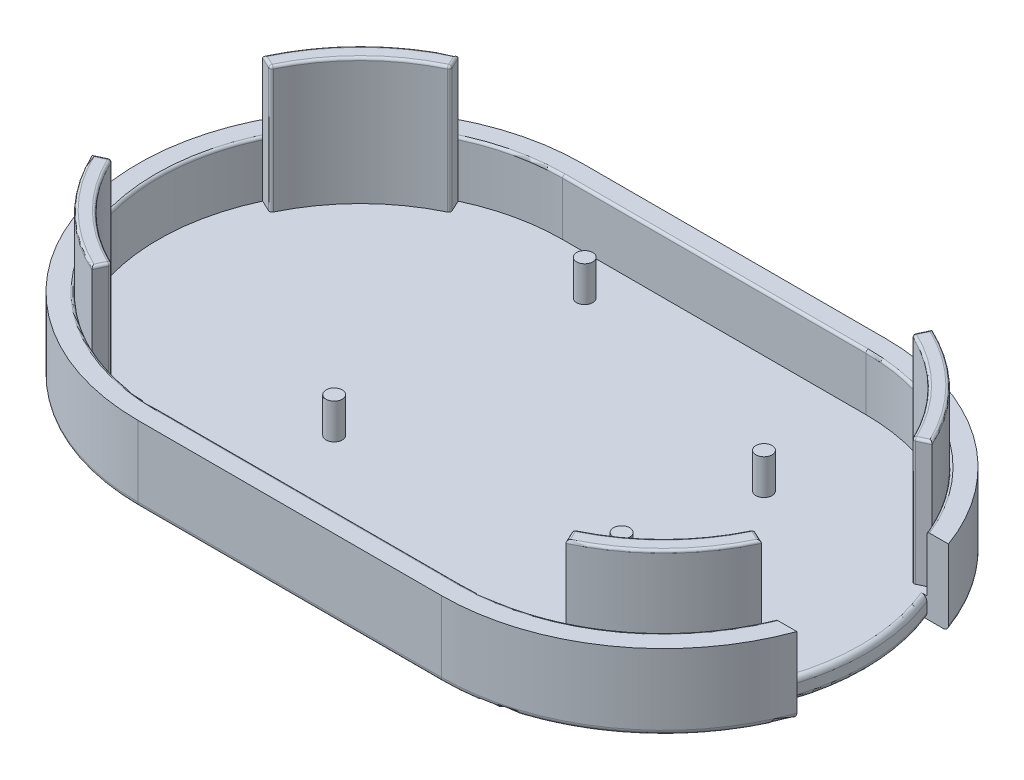
SolidWorks part; units mm, degrees
ref_plane "Front Plane" through (0, 0, 0) normal (0, 0, 1) x (1, 0, 0)
ref_plane "Top Plane" through (0, 0, 0) normal (0, 1, 0) x (1, 0, 0)
ref_plane "Right Plane" through (0, 0, 0) normal (1, 0, 0) x (0, 0, -1)
sketch "Sketch1" plane through (0, 0, 0) normal (0, 1, 0) x (1, 0, 0)
  line L1 (-30, 44) -> (30, 44)
  line L3 (30, -44) -> (-30, -44)
  arc A0 (30, -44) -> (30, 44) centre (30, 0) ccw
  arc A1 (-30, -44) -> (-30, 44) centre (-30, 0) cw
  point P10 (0, -44)
  point P11 (0, 44)
  dimension "D2" = 30
extrude "Boss-Extrude1" add sketch "Sketch1" along normal blind 15
shell "Shell1" thickness 4 removed face at (0, 15, 0)
fillet "Fillet1" radius 0.5 4 edges at (0, 15, 40) (-70, 15, 0) (0, 15, -40) (70, 15, 0)
sketch "Sketch5" plane through (0, 0, 0) normal (0, -1, 0) x (1, 0, 0)
  line L2 (30, 35) -> (-30, 35)
  line L3 (30, -35) -> (-30, -35)
  arc A1 (30, -35) -> (30, 35) centre (30, 0) ccw
  arc A2 (-30, 35) -> (-30, -35) centre (-30, 0) ccw
sketch "Sketch6" plane through (0, 0, 0) normal (0, 1, 0) x (1, 0, 0)
  line L0 (70, 0) -> (83, 0) construction
  line L1 (83, 0) -> (83, 15) construction
  line L2 (83, 0) -> (83, -15) construction
  line L3 (83, 15) -> (67.081, 15)
  line L4 (83, 15) -> (83, -15)
  line L5 (83, -15) -> (67.081, -15)
  arc A0 (67.081, -15) -> (67.081, 15) centre (30, 0) ccw
extrude "Cut-Extrude7" cut sketch "Sketch6" along normal through all
sketch "Sketch9" plane through (0, 4, 0) normal (0, 1, 0) x (1, 0, 0)
  line L0 (0, 0) -> (0, 8) construction
  line L1 (70, 0) -> (-70, 0) construction
  line L3 (0, 8) -> (33.03, 8) construction
  line L5 (33.03, 8) -> (33.03, 16.83) construction
  line L6 (33.03, 8) -> (33.03, -11.34) construction
  line L7 (0, 8) -> (-17.78, 8) construction
  line L8 (-17.78, 8) -> (-17.78, 32.16) construction
  line L9 (-17.78, 8) -> (-19.03, 8) construction
  line L10 (-19.03, 8) -> (-19.03, -16.16) construction
  circle A2 centre (33.03, 16.83) radius 1.6
  circle A3 centre (33.03, -11.34) radius 1.6
  circle A4 centre (-17.78, 32.16) radius 1.6
  circle A5 centre (-19.03, -16.16) radius 1.6
  arc A6 (67.081, -15) -> (67.081, 15) centre (30, 0) ccw construction
  arc A7 (-30, 40) -> (-30, -40) centre (-30, 0) ccw construction
  dimension "D5" = 24.16
  dimension "D3" = 19.34
  dimension "D4" = 17.78
  dimension "D6" = 1.25
  dimension "D8" = 8
  dimension "D1" = 33.03
  dimension "D2" = 8.83
  dimension "D7" = 24.16
extrude "Boss-Extrude3" add sketch "Sketch9" along normal blind 7
sketch "Sketch10" plane through (0, 4, 0) normal (0, 1, 0) x (1, 0, 0)
  line L0 (70, 0) -> (-70, 0) construction
  line L1 (-30, 44) -> (-30, -44) construction
  line L2 (30, 44) -> (30, -44) construction
  line L3 (-45.6369, 33.5334) -> (-46.9047, 36.2523)
  line L4 (-63.5334, 15.6369) -> (-66.2523, 16.9047)
  line L5 (-45.6369, -33.5334) -> (-46.9047, -36.2523)
  line L6 (-63.5334, -15.6369) -> (-66.2523, -16.9047)
  line L7 (45.6369, 33.5334) -> (46.9047, 36.2523)
  line L8 (63.5334, 15.6369) -> (66.2523, 16.9047)
  line L9 (63.5334, -15.6369) -> (66.2523, -16.9047)
  line L10 (45.6369, -33.5334) -> (46.9047, -36.2523)
  arc A0 (67.081, -15) -> (67.081, 15) centre (30, 0) ccw construction
  arc A1 (-30, 40) -> (-30, -40) centre (-30, 0) ccw construction
  arc A2 (-46.9047, 36.2523) -> (-66.2523, 16.9047) centre (-30, 0) ccw
  arc A4 (-45.6369, 33.5334) -> (-63.5334, 15.6369) centre (-30, 0) ccw
  arc A5 (1.925, 24.0997) -> (0, 21.6564) centre (30, 0) ccw
  arc A6 (-63.5334, -15.6369) -> (-45.6369, -33.5334) centre (-30, 0) ccw
  arc A7 (45.6369, -33.5334) -> (63.5334, -15.6369) centre (30, 0) ccw
  arc A8 (46.9047, -36.2523) -> (66.2523, -16.9047) centre (30, 0) ccw
  arc A9 (-66.2523, -16.9047) -> (-46.9047, -36.2523) centre (-30, 0) ccw
  arc A10 (63.5334, 15.6369) -> (45.6369, 33.5334) centre (30, 0) ccw
  arc A11 (66.2523, 16.9047) -> (46.9047, 36.2523) centre (30, 0) ccw
  arc M12 (30, -40) -> (67.081, -15) centre (30, 0) ccw
  arc M14 (67.081, 15) -> (30, 40) centre (30, 0) ccw
  arc M16 (-30, 40) -> (-30, -40) centre (-30, 0) ccw
  dimension "D1" = 25
  dimension "D2" = 25
  dimension "D3" = 25
  dimension "D4" = 25
extrude "Boss-Extrude4" add sketch "Sketch10" along normal blind 25 contours A10 L8 L7 M14 | A7 L10 L9 M12 | A6 L6 L5 M16 | A2 L4 A4 L3 region at (-56.6876, 4, 26.6876) region at (56.6876, 4, -26.6876) region at (56.6876, 4, 26.6876)
fillet "Fillet2" radius 0.5 24 edges at (46.2708, 29, -34.8928) (58.2843, 29, -28.2843) (64.8928, 29, -16.2708) (56.163, 29, -26.163) (64.8928, 29, 16.2708) (58.2843, 29, 28.2843) (46.2708, 29, 34.8928) (56.163, 29, 26.163) (-46.2708, 29, 34.8928) (-58.2843, 29, 28.2843) (-64.8928, 29, 16.2708) (-56.163, 29, 26.163) (-56.163, 29, -26.163) (-64.8928, 29, -16.2708) (-58.2843, 29, -28.2843) (-46.2708, 29, -34.8928) (45.6369, 16.5, 33.5334) (63.5334, 16.5, 15.6369) (-45.6369, 16.5, 33.5334) (-63.5334, 16.5, 15.6369) (-63.5334, 16.5, -15.6369) (-45.6369, 16.5, -33.5334) (45.6369, 16.5, -33.5334) (63.5334, 16.5, -15.6369)
fillet "Fillet3" radius 1 7 edges at (55.2587, 0, -36.0278) (0, 0, -44) (-74, 0, 0) (55.2587, 0, 36.0278) (70, 4, 0) (70, 0, 0) (0, 0, 44)
